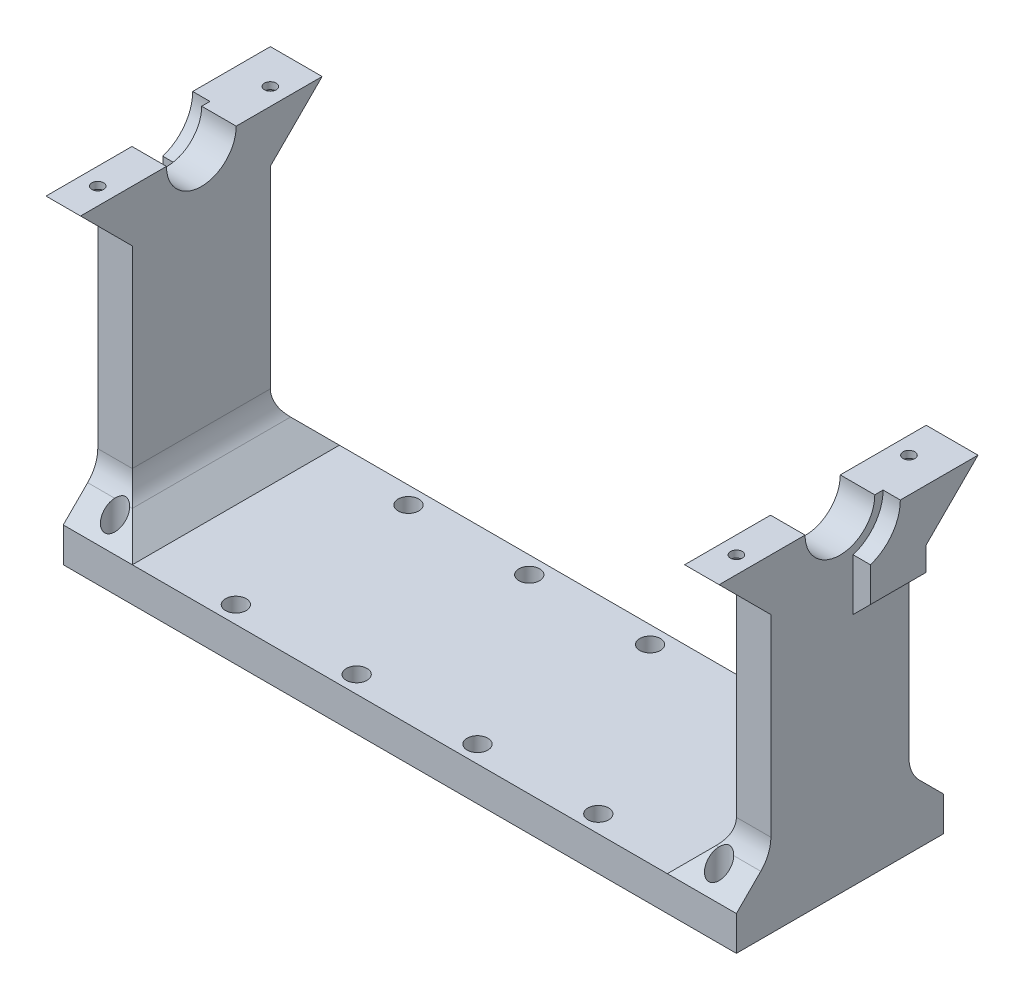
SolidWorks part; units mm, degrees
ref_plane "Front Plane" through (0, 0, 0) normal (0, 0, 1) x (1, 0, 0)
ref_plane "Top Plane" through (0, 0, 0) normal (0, 1, 0) x (1, 0, 0)
ref_plane "Right Plane" through (0, 0, 0) normal (1, 0, 0) x (0, 0, -1)
sketch "Sketch1" plane through (0, 0, 0) normal (0, 1, 0) x (1, 0, 0)
  line L1 (-97.5, -50) -> (97.5, -50)
  line L2 (-97.5, -50) -> (-97.5, 50)
  line L3 (-97.5, 50) -> (97.5, 50)
  line L4 (97.5, -50) -> (97.5, 50)
  line L5 (-97.5, -50) -> (97.5, 50) construction
  line L6 (-97.5, 50) -> (97.5, -50) construction
  point P0 (0, 0)
  dimension "D1" = 195
  dimension "D2" = 100
extrude "Boss-Extrude1" add sketch "Sketch1" along normal blind 10
sketch "Sketch2" plane through (0, 0, 0) normal (0, 0, 1) x (1, 0, 0)
  line L0 (97.5, 10) -> (97.5, 0) construction
  line L1 (97.5, 10) -> (97.5, 95)
  line L2 (-97.5, 10) -> (97.5, 10) construction
  line L3 (97.5, 95) -> (87.5, 95)
  line L4 (87.5, 95) -> (87.5, 10)
  line L5 (87.5, 10) -> (97.5, 10)
  dimension "D3" = 10
  dimension "D4" = 85
extrude "Boss-Extrude2" add sketch "Sketch2" along normal mid plane 40
sketch "Sketch4" plane through (97.5, 0, 0) normal (1, 0, 0) x (0, 0, -1)
  line L0 (-20, 80) -> (-35, 95)
  line L1 (-20, 10) -> (-20, 95) construction
  line L2 (-35, 95) -> (-20, 95)
  line L3 (-20, 95) -> (-20, 80)
  line L4 (-20, 95) -> (20, 95) construction
  dimension "D1" = 15
  dimension "D2" = 45
extrude "Boss-Extrude3" add sketch "Sketch4" against normal blind 10
sketch "Sketch5" plane through (0, 95, 0) normal (0, 1, 0) x (1, 0, 0)
  line L0 (87.5, -35) -> (97.5, -35) construction
  line L1 (92.5, -25) -> (92.5, -32.6482) construction
  circle A0 centre (92.5, -25) radius 1.7
  point P4 (92.5, -35)
  dimension "D1" = 3.4
  dimension "D2" = 10
extrude "Cut-Extrude2" cut sketch "Sketch5" against normal up to surface and the other way through all up to face at (92.5, 87.5, 27.5)
mirror "Mirror2" about plane through (0, 0, 0) normal (1, 0, 0) of "Boss-Extrude2"
sketch "Sketch3" plane through (97.5, 0, 0) normal (1, 0, 0) x (0, 0, -1)
  line L0 (-35, 95) -> (20, 95) construction
  line L1 (-10.1, 95) -> (10.1, 95)
  arc A0 (-10.1, 95) -> (10.1, 95) centre (0, 95) ccw
  dimension "D1" = 10.1
extrude "Cut-Extrude1" cut sketch "Sketch3" against normal through all both and the other way through all
mirror "Mirror6" about plane through (0, 0, 0) normal (1, 0, 0) of "Boss-Extrude3", "Cut-Extrude2" second plane through (0, 0, 0) second plane normal (0, 0, 1)
sketch "Sketch7" plane through (0, 10, 0) normal (0, 1, 0) x (1, 0, 0)
  line L0 (-97.5, -20) -> (97.5, -20)
  line L1 (-97.5, 50) -> (-97.5, 20) construction
  line L2 (97.5, -50) -> (97.5, -20) construction
  line L3 (97.5, 20) -> (-97.5, 20)
  line L4 (-87.5, 20) -> (-97.5, 20) construction
  line L5 (-87.5, -20) -> (-97.5, -20) construction
  line L6 (-97.5, -20) -> (-97.5, 12.5)
  line L7 (97.5, 20) -> (97.5, -12.5)
  line L8 (97.5, -50) -> (97.5, -20)
  line L9 (97.5, 50) -> (-97.5, 50)
  line L10 (-97.5, 50) -> (-97.5, 20)
  line L11 (-97.5, -50) -> (97.5, -50)
  line L12 (97.5, -50) -> (97.5, -20)
  line L13 (97.5, 50) -> (-97.5, 50)
  line L14 (-97.5, 50) -> (-97.5, 20)
  line L15 (-97.5, -50) -> (97.5, -50)
  line L28 (-87.5, 20) -> (-87.5, -20)
  line L29 (-87.5, 20) -> (-87.5, -20)
  line L30 (-87.5, -20) -> (-97.5, -20)
  line L31 (-87.5, -20) -> (-97.5, -20)
  line L32 (-97.5, -20) -> (-97.5, -50)
  line L33 (-97.5, -20) -> (-97.5, -50)
  line L34 (97.5, -20) -> (87.5, -20)
  line L35 (97.5, -20) -> (87.5, -20)
  line L36 (87.5, -20) -> (87.5, 20)
  line L37 (87.5, -20) -> (87.5, 20)
  line L38 (87.5, 20) -> (97.5, 20)
  line L39 (87.5, 20) -> (97.5, 20)
  line L40 (97.5, 20) -> (97.5, 50)
  line L41 (97.5, 20) -> (97.5, 50)
  line L42 (-97.5, 20) -> (-87.5, 20)
  line L43 (-97.5, 20) -> (-87.5, 20)
  line M9 (-87.5, -20) -> (-97.5, -20)
  line M10 (-97.5, -20) -> (-97.5, -50)
  line M11 (-97.5, 20) -> (-87.5, 20)
  line M12 (97.5, 20) -> (97.5, 50)
  line M13 (97.5, -20) -> (87.5, -20)
  line M15 (87.5, 20) -> (97.5, 20)
  line M16 (97.5, -50) -> (97.5, -20)
  line M17 (97.5, 50) -> (-97.5, 50)
  line M18 (-97.5, 50) -> (-97.5, 20)
  line M19 (-97.5, -50) -> (97.5, -50)
  dimension "D1" = 0
extrude "Cut-Extrude3" cut sketch "Sketch7" against normal up to surface (10 mm away) contours L3 M15 M12 M17 M18 M11 | L0 M9 M10 M19 M16 M13 up to face at (0, 0, 0)
sketch "Sketch9" plane through (97.5, 0, 0) normal (1, 0, 0) x (0, 0, -1)
  line L0 (0, 0) -> (0, 109.6863) construction
  line L1 (3.825, 83.0996) -> (3.825, 73.0996)
  line L2 (3.825, 73.0996) -> (20, 73.0996)
  line L5 (12.5, 95) -> (20, 95)
  line L6 (10.1, 95) -> (35, 95) construction
  line L7 (20, 95) -> (20, 73.0996)
  line L8 (20, 0) -> (20, 80) construction
  arc A2 (3.825, 83.0996) -> (12.5, 95) centre (0, 95) ccw
  arc A4 (-10.1, 95) -> (10.1, 95) centre (0, 95) ccw construction
  dimension "D3" = 12.5
  dimension "D1" = 3.825
  dimension "D2" = 10
extrude "Boss-Extrude5" add sketch "Sketch9" along normal blind 5
mirror "Mirror9" about plane through (0, 0, 0) normal (1, 0, 0) of "Boss-Extrude5"
chamfer "Chamfer3" distance 5 angle 45 3 edges at (-97.5, 73.0996, -11.9125) (-100, 73.0996, -3.825) (97.5, 73.0996, -11.9125)
sketch "Sketch11" plane through (-97.5, 0, 0) normal (-1, 0, 0) x (0, 0, 1)
  line L3 (-20, 80) -> (-20, 95)
  line L4 (-20, 95) -> (-35, 95)
  line L5 (-35, 95) -> (-20, 80)
  line L6 (-20, 80) -> (-20, 95)
  line L7 (-20, 95) -> (-35, 95)
  line L8 (-35, 95) -> (-20, 80)
  dimension "D1" = 0
extrude "Boss-Extrude6" add sketch "Sketch11" along normal up to surface (5 mm away) up to face at (-102.5, 83.5771, -12.4177)
sketch "Sketch12" plane through (97.5, 0, 0) normal (1, 0, 0) x (0, 0, -1)
  line L3 (20, 95) -> (20, 80)
  line L4 (20, 80) -> (35, 95)
  line L5 (35, 95) -> (20, 95)
  line L6 (20, 95) -> (20, 80)
  line L7 (20, 80) -> (35, 95)
  line L8 (35, 95) -> (20, 95)
  dimension "D1" = 0
extrude "Boss-Extrude7" add sketch "Sketch12" along normal up to surface (5 mm away) up to face at (102.5, 83.5771, -12.4177)
sketch "Sketch13" plane through (0, 95, 0) normal (0, 1, 0) x (1, 0, 0)
  line L1 (89.3246, -25) -> (90.9123, -27.75)
  line L2 (90.9123, -27.75) -> (94.0877, -27.75)
  line L3 (94.0877, -27.75) -> (95.6754, -25)
  line L4 (95.6754, -25) -> (94.0877, -22.25)
  line L5 (94.0877, -22.25) -> (90.9123, -22.25)
  line L6 (90.9123, -22.25) -> (89.3246, -25)
  circle A0 centre (92.5, -25) radius 2.75 construction
  dimension "D1" = 5.5
extrude "Cut-Extrude4" cut sketch "Sketch13" against normal blind 4 from offset 2 offset against normal yes
sketch "Sketch15" plane through (0, 0, 22.25) normal (0, 0, 1) x (1, 0, 0)
  line L0 (89.3246, 89) -> (89.3246, 93) construction
  line L1 (89.3246, 93) -> (95.6754, 93)
  line L2 (89.3246, 93) -> (89.3246, 89)
  line L3 (89.3246, 89) -> (95.6754, 89)
  line L4 (95.6754, 93) -> (95.6754, 89)
  line L5 (95.6754, 89) -> (95.6754, 93) construction
  line L6 (94.0877, 89) -> (90.9123, 89) construction
  line L8 (94.0877, 93) -> (90.9123, 93) construction
extrude "Cut-Extrude5" cut sketch "Sketch15" along normal through all from offset 2.75
mirror "Mirror10" about plane through (0, 0, 0) normal (1, 0, 0) of "Cut-Extrude4", "Cut-Extrude5" second plane through (0, 0, 0) second plane normal (0, 0, 1)
sketch "Sketch16" plane through (0, 10, 0) normal (0, 1, 0) x (1, 0, 0)
  line L0 (97.5, -20) -> (97.5, 20) construction
  line L1 (-97.5, -20) -> (97.5, -20)
  line L2 (-97.5, -20) -> (-97.5, -30)
  line L3 (-97.5, -30) -> (97.5, -30)
  line L4 (97.5, -20) -> (97.5, -30)
  line L5 (-97.5, 20) -> (-97.5, -20) construction
  line L6 (-87.5, -20) -> (87.5, -20) construction
  dimension "D1" = 10
extrude "Boss-Extrude8" add sketch "Sketch16" against normal up to surface (10 mm away) up to face at (0, 0, 0)
sketch "Sketch17" plane through (0, 10, 0) normal (0, 1, 0) x (1, 0, 0)
  line L0 (-97.5, -20) -> (-97.5, -30) construction
  circle A0 centre (-87.5, -25) radius 1.7
  point P6 (-97.5, -25)
  dimension "D1" = 3.4
  dimension "D2" = 10
extrude "Cut-Extrude6" cut sketch "Sketch17" against normal blind 10
sketch "Sketch18" plane through (0, 10, 0) normal (0, 1, 0) x (1, 0, 0)
  circle A0 centre (-87.5, -25) radius 3
  dimension "D1" = 6
extrude "Cut-Extrude7" cut sketch "Sketch18" against normal offset from surface (7 mm away) 3 up to face at (-87.5, 0, 26.7)
pattern_linear "LPattern2" count 3 spacing 35 along (1, 0, 0) of "Cut-Extrude7", "Cut-Extrude6"
mirror "Mirror11" about plane through (0, 0, 0) normal (1, 0, 0) of "Cut-Extrude6", "Cut-Extrude7", "LPattern2"
mirror "Mirror12" about plane through (0, 0, 0) normal (0, 0, 1) of "Mirror11", "LPattern2", "Cut-Extrude7", "Cut-Extrude6", "Boss-Extrude8"
chamfer "Chamfer5" distance 10 angle 45 7 edges at (-92.5, 10, 20) (-92.5, 10, -20) (-97.5, 10, -25) (-87.5, 10, 0) (92.5, 10, 20) (92.5, 10, -20) (87.5, 10, 0)
fillet "Fillet1" radius 10 6 edges at (-92.5, 20, 20) (-92.5, 20, -20) (-87.5, 20, 0) (92.5, 20, 20) (92.5, 20, -20) (87.5, 20, 0)
